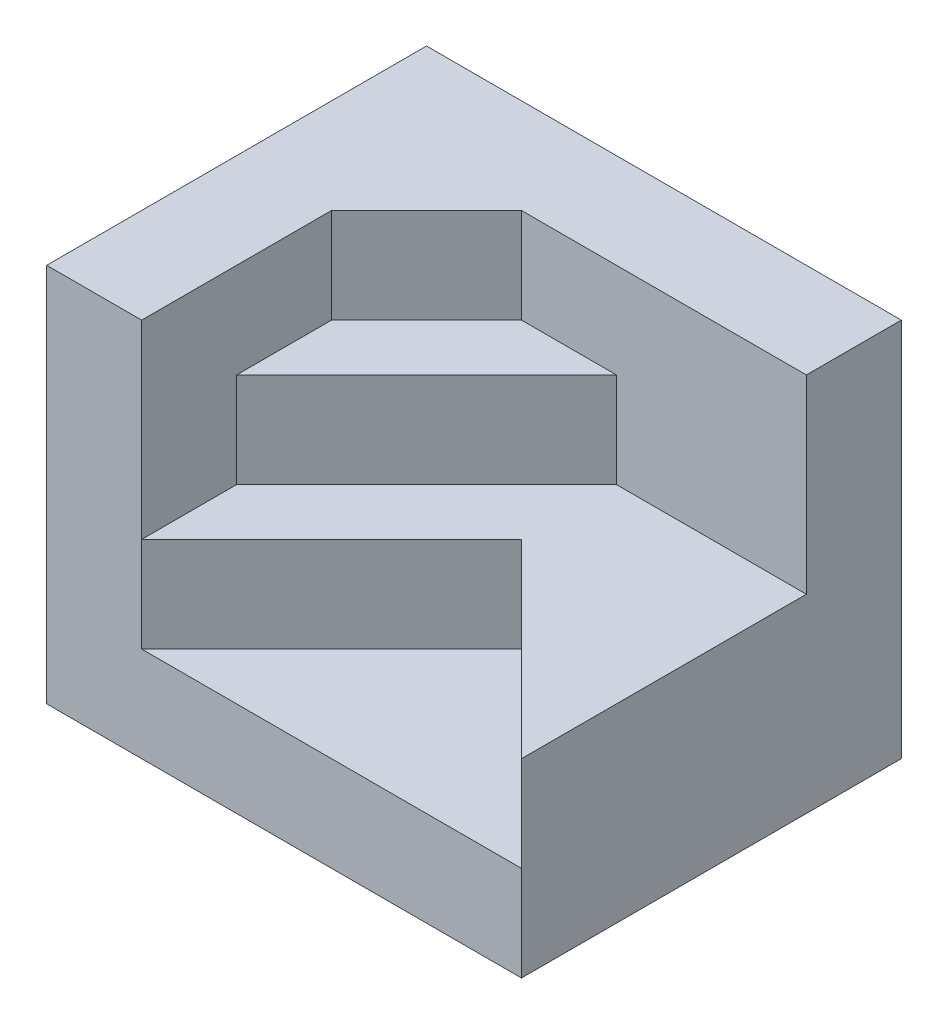
SolidWorks part; units mm, degrees
ref_plane "前基準面" through (0, 0, 0) normal (0, 0, 1) x (1, 0, 0)
ref_plane "上基準面" through (0, 0, 0) normal (0, 1, 0) x (1, 0, 0)
ref_plane "右基準面" through (0, 0, 0) normal (1, 0, 0) x (0, 0, -1)
sketch "草圖1" plane through (0, 0, 0) normal (0, 1, 0) x (1, 0, 0)
  line L0 (-1.5, -2) -> (-1.5, 1)
  line L1 (-2.5, -2) -> (2.5, -2)
  line L2 (-2.5, -2) -> (-2.5, 2)
  line L3 (-2.5, 2) -> (2.5, 2)
  line L4 (2.5, -2) -> (2.5, 2)
  line L5 (-2.5, -2) -> (2.5, 2) construction
  line L6 (-2.5, 2) -> (2.5, -2) construction
  line L7 (-1.5, 1) -> (2.5, 1)
  line L8 (-1.5, 0) -> (-0.5, 1)
  line L9 (-0.5, 1) -> (0.5, 1)
  line L10 (0.5, 1) -> (-1.5, -1)
  line L11 (-1.5, -1) -> (-1.5, -2)
  line L12 (-1.5, -2) -> (0.5, 0)
  line L13 (0.5, 0) -> (2.5, -2)
  point P0 (0, 0)
  dimension "D1" = 4
  dimension "D2" = 5
  dimension "D3" = 1
  dimension "D4" = 1
  dimension "D5" = 1
  dimension "D6" = 1
  dimension "D7" = 1
  dimension "D8" = 1
  dimension "D9" = 2
  dimension "D10" = 2
extrude "填料-伸長2" add sketch "草圖1" along normal blind 4 contours L0 L7 L4 L3 L2 L1 | L0 L8 L7 region at (-2, 0, 1.936) region at (-1.1667, 0, -0.6667)
extrude "填料-伸長3" add sketch "草圖1<4>" along normal blind 3 contours L10 L7 L8 L0 region at (-0.7222, 0, -0.2222)
sketch "草圖1<4>" plane through (0, 0, 0) normal (0, 1, 0) x (1, 0, 0) same geometry as "草圖1"
extrude "填料-伸長4" add sketch "草圖1<5>" along normal blind 2 contours L12 L13 L4 L7 L10 L0 region at (0.9444, 0, 0.2222)
sketch "草圖1<5>" plane through (0, 0, 0) normal (0, 1, 0) x (1, 0, 0) same geometry as "草圖1"
extrude "填料-伸長5" add sketch "草圖1<6>" along normal blind 1 contours L13 L12 L1 region at (0.5, 0, 1.3333)
sketch "草圖1<6>" plane through (0, 0, 0) normal (0, 1, 0) x (1, 0, 0) same geometry as "草圖1"
